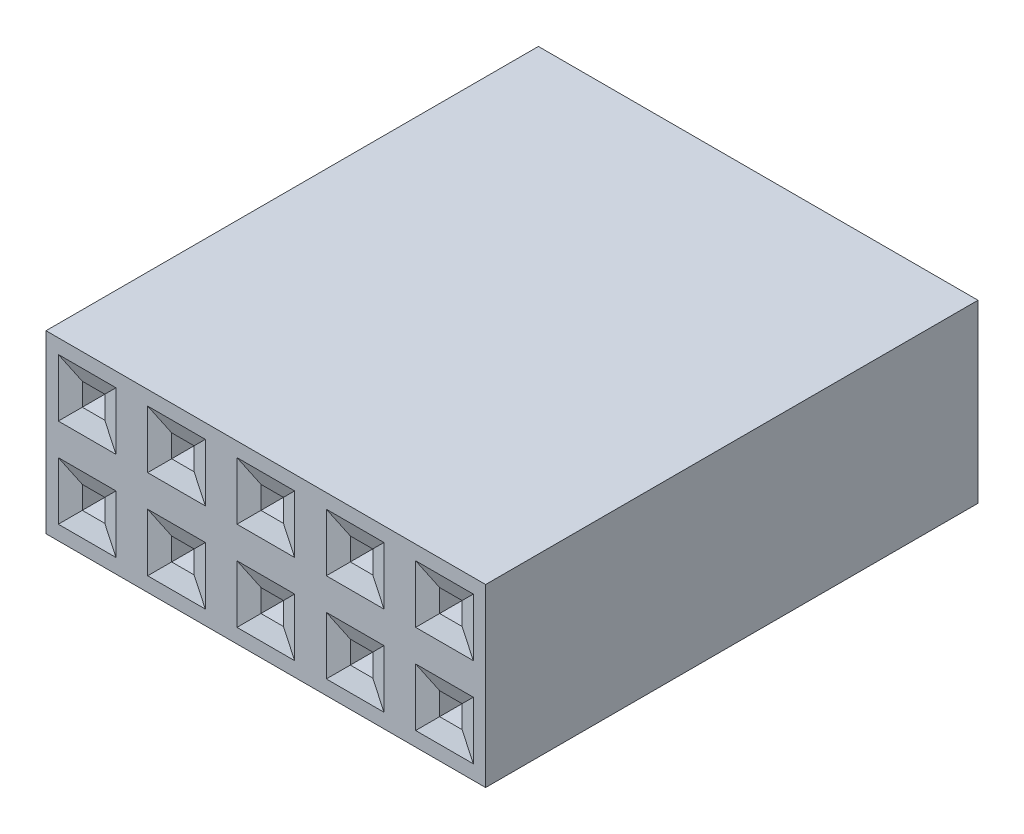
SolidWorks part; units mm, degrees
ref_plane "Front Plane" through (0, 0, 0) normal (0, 0, 1) x (1, 0, 0)
ref_plane "Top Plane" through (0, 0, 0) normal (0, 1, 0) x (1, 0, 0)
ref_plane "Right Plane" through (0, 0, 0) normal (1, 0, 0) x (0, 0, -1)
sketch "Sketch1" plane through (0, 0, 0) normal (0, 1, 0) x (1, 0, 0)
  line L1 (-6.25, 7) -> (6.25, 7)
  line L2 (-6.25, 7) -> (-6.25, -7)
  line L3 (-6.25, -7) -> (6.25, -7)
  line L4 (6.25, 7) -> (6.25, -7)
  line L5 (-6.25, 7) -> (6.25, -7) construction
  line L6 (-6.25, -7) -> (6.25, 7) construction
  point P0 (0, 0)
  dimension "D1" = 14
  dimension "D2" = 12.5
extrude "Boss-Extrude1" add sketch "Sketch1" along normal blind 5
sketch "Sketch3" plane through (0, 0, 7) normal (0, 0, 1) x (1, 0, 0)
  line L0 (-5.4, 0.91) -> (-5.4, 1.55) construction
  line L1 (-5.4, 1.55) -> (-4.76, 1.55) construction
  line L2 (-4.76, 0.91) -> (-5.4, 0.91) construction
  line L3 (-4.76, 1.55) -> (-4.76, 0.91) construction
  line L12 (-2.22, 0.91) -> (-2.86, 0.91) construction
  line L13 (-2.22, 1.55) -> (-2.22, 0.91) construction
  line L14 (-2.86, 1.55) -> (-2.22, 1.55) construction
  line L15 (-2.86, 0.91) -> (-2.86, 1.55) construction
  line L16 (0.32, 0.91) -> (-0.32, 0.91) construction
  line L17 (-0.32, 0.91) -> (-0.32, 1.55) construction
  line L18 (0.32, 1.55) -> (0.32, 0.91) construction
  line L19 (-0.32, 1.55) -> (0.32, 1.55) construction
  line L20 (2.86, 1.55) -> (2.86, 0.91) construction
  line L21 (2.22, 1.55) -> (2.86, 1.55) construction
  line L22 (2.86, 0.91) -> (2.22, 0.91) construction
  line L23 (2.22, 0.91) -> (2.22, 1.55) construction
  line L24 (5.4, 0.91) -> (4.76, 0.91) construction
  line L25 (4.76, 0.91) -> (4.76, 1.55) construction
  line L26 (5.4, 1.55) -> (5.4, 0.91) construction
  line L27 (4.76, 1.55) -> (5.4, 1.55) construction
  line L28 (5.4, 4.09) -> (5.4, 3.45) construction
  line L29 (4.76, 4.09) -> (5.4, 4.09) construction
  line L30 (5.4, 3.45) -> (4.76, 3.45) construction
  line L31 (4.76, 3.45) -> (4.76, 4.09) construction
  line L32 (2.86, 3.45) -> (2.22, 3.45) construction
  line L33 (2.22, 3.45) -> (2.22, 4.09) construction
  line L34 (0.32, 3.45) -> (-0.32, 3.45) construction
  line L35 (-0.32, 3.45) -> (-0.32, 4.09) construction
  line L36 (2.86, 4.09) -> (2.86, 3.45) construction
  line L37 (2.22, 4.09) -> (2.86, 4.09) construction
  line L38 (0.32, 4.09) -> (0.32, 3.45) construction
  line L39 (-0.32, 4.09) -> (0.32, 4.09) construction
  line L40 (-2.22, 4.09) -> (-2.22, 3.45) construction
  line L41 (-2.86, 4.09) -> (-2.22, 4.09) construction
  line L42 (-2.86, 3.45) -> (-2.86, 4.09) construction
  line L43 (-2.22, 3.45) -> (-2.86, 3.45) construction
  line L44 (-5.4, 3.45) -> (-5.4, 4.09) construction
  line L45 (-4.76, 3.45) -> (-5.4, 3.45) construction
  line L46 (-4.76, 4.09) -> (-4.76, 3.45) construction
  line L47 (-5.4, 4.09) -> (-4.76, 4.09) construction
  line L48 (-5.4, 0.91) -> (-5.4, 1.55)
  line L49 (-5.4, 1.55) -> (-4.76, 1.55)
  line L50 (-4.76, 0.91) -> (-5.4, 0.91)
  line L51 (-4.76, 1.55) -> (-4.76, 0.91)
  line L52 (-2.22, 0.91) -> (-2.86, 0.91)
  line L53 (-2.22, 1.55) -> (-2.22, 0.91)
  line L54 (-2.86, 1.55) -> (-2.22, 1.55)
  line L55 (-2.86, 0.91) -> (-2.86, 1.55)
  line L56 (0.32, 0.91) -> (-0.32, 0.91)
  line L57 (-0.32, 0.91) -> (-0.32, 1.55)
  line L58 (0.32, 1.55) -> (0.32, 0.91)
  line L59 (-0.32, 1.55) -> (0.32, 1.55)
  line L60 (2.86, 1.55) -> (2.86, 0.91)
  line L61 (2.22, 1.55) -> (2.86, 1.55)
  line L62 (2.86, 0.91) -> (2.22, 0.91)
  line L63 (2.22, 0.91) -> (2.22, 1.55)
  line L64 (5.4, 0.91) -> (4.76, 0.91)
  line L65 (4.76, 0.91) -> (4.76, 1.55)
  line L66 (5.4, 1.55) -> (5.4, 0.91)
  line L67 (4.76, 1.55) -> (5.4, 1.55)
  line L68 (5.4, 4.09) -> (5.4, 3.45)
  line L69 (4.76, 4.09) -> (5.4, 4.09)
  line L70 (5.4, 3.45) -> (4.76, 3.45)
  line L71 (4.76, 3.45) -> (4.76, 4.09)
  line L72 (2.86, 3.45) -> (2.22, 3.45)
  line L73 (2.22, 3.45) -> (2.22, 4.09)
  line L74 (0.32, 3.45) -> (-0.32, 3.45)
  line L75 (-0.32, 3.45) -> (-0.32, 4.09)
  line L76 (2.86, 4.09) -> (2.86, 3.45)
  line L77 (2.22, 4.09) -> (2.86, 4.09)
  line L78 (0.32, 4.09) -> (0.32, 3.45)
  line L79 (-0.32, 4.09) -> (0.32, 4.09)
  line L80 (-2.22, 4.09) -> (-2.22, 3.45)
  line L81 (-2.86, 4.09) -> (-2.22, 4.09)
  line L82 (-2.86, 3.45) -> (-2.86, 4.09)
  line L83 (-2.22, 3.45) -> (-2.86, 3.45)
  line L84 (-5.4, 3.45) -> (-5.4, 4.09)
  line L85 (-4.76, 3.45) -> (-5.4, 3.45)
  line L86 (-4.76, 4.09) -> (-4.76, 3.45)
  line L87 (-5.4, 4.09) -> (-4.76, 4.09)
extrude "Cut-Extrude1" cut sketch "Sketch3" against normal up to surface (4.5 mm away)
chamfer "Chamfer1" distance 0.5 angle 20 40 edges at (-5.4, 1.23, 7) (-5.08, 0.91, 7) (-4.76, 1.23, 7) (-5.08, 1.55, 7) (-2.22, 1.23, 7) (-2.54, 0.91, 7) (-2.86, 1.23, 7) (-2.54, 1.55, 7) (-0.32, 1.23, 7) (0, 0.91, 7) (0.32, 1.23, 7) (0, 1.55, 7) (2.22, 1.23, 7) (2.54, 0.91, 7) (2.86, 1.23, 7) (2.54, 1.55, 7) (4.76, 1.23, 7) (5.08, 0.91, 7) (5.4, 1.23, 7) (5.08, 1.55, 7) (4.76, 3.77, 7) (5.08, 3.45, 7) (5.4, 3.77, 7) (5.08, 4.09, 7) (2.54, 3.45, 7) (2.86, 3.77, 7) (2.22, 3.77, 7) (2.54, 4.09, 7) (0.32, 3.77, 7) (0, 3.45, 7) (-0.32, 3.77, 7) (0, 4.09, 7) (-2.22, 3.77, 7) (-2.54, 4.09, 7) (-2.86, 3.77, 7) (-2.54, 3.45, 7) (-5.4, 3.77, 7) (-5.08, 4.09, 7) (-4.76, 3.77, 7) (-5.08, 3.45, 7) first distance on face at (-5.08, 3.77, 7)
sketch "Sketch4" plane through (0, 0, -7) normal (0, 0, -1) x (-1, 0, 0)
  line L0 (-4.26, 2.05) -> (-5.9, 2.05) construction
  line L1 (-5.9, 2.05) -> (-5.9, 0.41) construction
  line L2 (-5.9, 0.41) -> (-4.26, 0.41) construction
  line L3 (-4.26, 0.41) -> (-4.26, 2.05) construction
  line L4 (-3.36, 0.41) -> (-1.72, 0.41) construction
  line L5 (-1.72, 0.41) -> (-1.72, 2.05) construction
  line L6 (-1.72, 2.05) -> (-3.36, 2.05) construction
  line L7 (-3.36, 2.05) -> (-3.36, 0.41) construction
  line L8 (-0.82, 2.05) -> (-0.82, 0.41) construction
  line L9 (-0.82, 0.41) -> (0.82, 0.41) construction
  line L10 (0.82, 0.41) -> (0.82, 2.05) construction
  line L11 (0.82, 2.05) -> (-0.82, 2.05) construction
  line L12 (3.36, 2.05) -> (1.72, 2.05) construction
  line L13 (1.72, 2.05) -> (1.72, 0.41) construction
  line L14 (1.72, 0.41) -> (3.36, 0.41) construction
  line L15 (3.36, 0.41) -> (3.36, 2.05) construction
  line L16 (4.26, 0.41) -> (5.9, 0.41) construction
  line L17 (5.9, 0.41) -> (5.9, 2.05) construction
  line L18 (4.26, 2.05) -> (4.26, 0.41) construction
  line L19 (5.9, 2.05) -> (4.26, 2.05) construction
  line L20 (4.26, 2.95) -> (5.9, 2.95) construction
  line L21 (5.9, 2.95) -> (5.9, 4.59) construction
  line L22 (5.9, 4.59) -> (4.26, 4.59) construction
  line L23 (4.26, 4.59) -> (4.26, 2.95) construction
  line L24 (1.72, 2.95) -> (3.36, 2.95) construction
  line L25 (3.36, 2.95) -> (3.36, 4.59) construction
  line L26 (3.36, 4.59) -> (1.72, 4.59) construction
  line L27 (1.72, 4.59) -> (1.72, 2.95) construction
  line L28 (-0.82, 2.95) -> (0.82, 2.95) construction
  line L29 (0.82, 2.95) -> (0.82, 4.59) construction
  line L30 (0.82, 4.59) -> (-0.82, 4.59) construction
  line L31 (-0.82, 4.59) -> (-0.82, 2.95) construction
  line L32 (-3.36, 2.95) -> (-1.72, 2.95) construction
  line L33 (-1.72, 2.95) -> (-1.72, 4.59) construction
  line L34 (-1.72, 4.59) -> (-3.36, 4.59) construction
  line L35 (-3.36, 4.59) -> (-3.36, 2.95) construction
  line L36 (-5.9, 2.95) -> (-4.26, 2.95) construction
  line L37 (-5.9, 4.59) -> (-5.9, 2.95) construction
  line L38 (-4.26, 2.95) -> (-4.26, 4.59) construction
  line L39 (-4.26, 4.59) -> (-5.9, 4.59) construction
  line L40 (-4.26, 2.05) -> (-5.9, 2.05)
  line L41 (-5.9, 2.05) -> (-5.9, 0.41)
  line L42 (-5.9, 0.41) -> (-4.26, 0.41)
  line L43 (-4.26, 0.41) -> (-4.26, 2.05)
  line L44 (-3.36, 0.41) -> (-1.72, 0.41)
  line L45 (-1.72, 0.41) -> (-1.72, 2.05)
  line L46 (-1.72, 2.05) -> (-3.36, 2.05)
  line L47 (-3.36, 2.05) -> (-3.36, 0.41)
  line L48 (-0.82, 2.05) -> (-0.82, 0.41)
  line L49 (-0.82, 0.41) -> (0.82, 0.41)
  line L50 (0.82, 0.41) -> (0.82, 2.05)
  line L51 (0.82, 2.05) -> (-0.82, 2.05)
  line L52 (3.36, 2.05) -> (1.72, 2.05)
  line L53 (1.72, 2.05) -> (1.72, 0.41)
  line L54 (1.72, 0.41) -> (3.36, 0.41)
  line L55 (3.36, 0.41) -> (3.36, 2.05)
  line L56 (4.26, 0.41) -> (5.9, 0.41)
  line L57 (5.9, 0.41) -> (5.9, 2.05)
  line L58 (4.26, 2.05) -> (4.26, 0.41)
  line L59 (5.9, 2.05) -> (4.26, 2.05)
  line L60 (4.26, 2.95) -> (5.9, 2.95)
  line L61 (5.9, 2.95) -> (5.9, 4.59)
  line L62 (5.9, 4.59) -> (4.26, 4.59)
  line L63 (4.26, 4.59) -> (4.26, 2.95)
  line L64 (1.72, 2.95) -> (3.36, 2.95)
  line L65 (3.36, 2.95) -> (3.36, 4.59)
  line L66 (3.36, 4.59) -> (1.72, 4.59)
  line L67 (1.72, 4.59) -> (1.72, 2.95)
  line L68 (-0.82, 2.95) -> (0.82, 2.95)
  line L69 (0.82, 2.95) -> (0.82, 4.59)
  line L70 (0.82, 4.59) -> (-0.82, 4.59)
  line L71 (-0.82, 4.59) -> (-0.82, 2.95)
  line L72 (-3.36, 2.95) -> (-1.72, 2.95)
  line L73 (-1.72, 2.95) -> (-1.72, 4.59)
  line L74 (-1.72, 4.59) -> (-3.36, 4.59)
  line L75 (-3.36, 4.59) -> (-3.36, 2.95)
  line L76 (-5.9, 2.95) -> (-4.26, 2.95)
  line L77 (-5.9, 4.59) -> (-5.9, 2.95)
  line L78 (-4.26, 2.95) -> (-4.26, 4.59)
  line L79 (-4.26, 4.59) -> (-5.9, 4.59)
extrude "Cut-Extrude2" cut sketch "Sketch4" against normal blind 6
